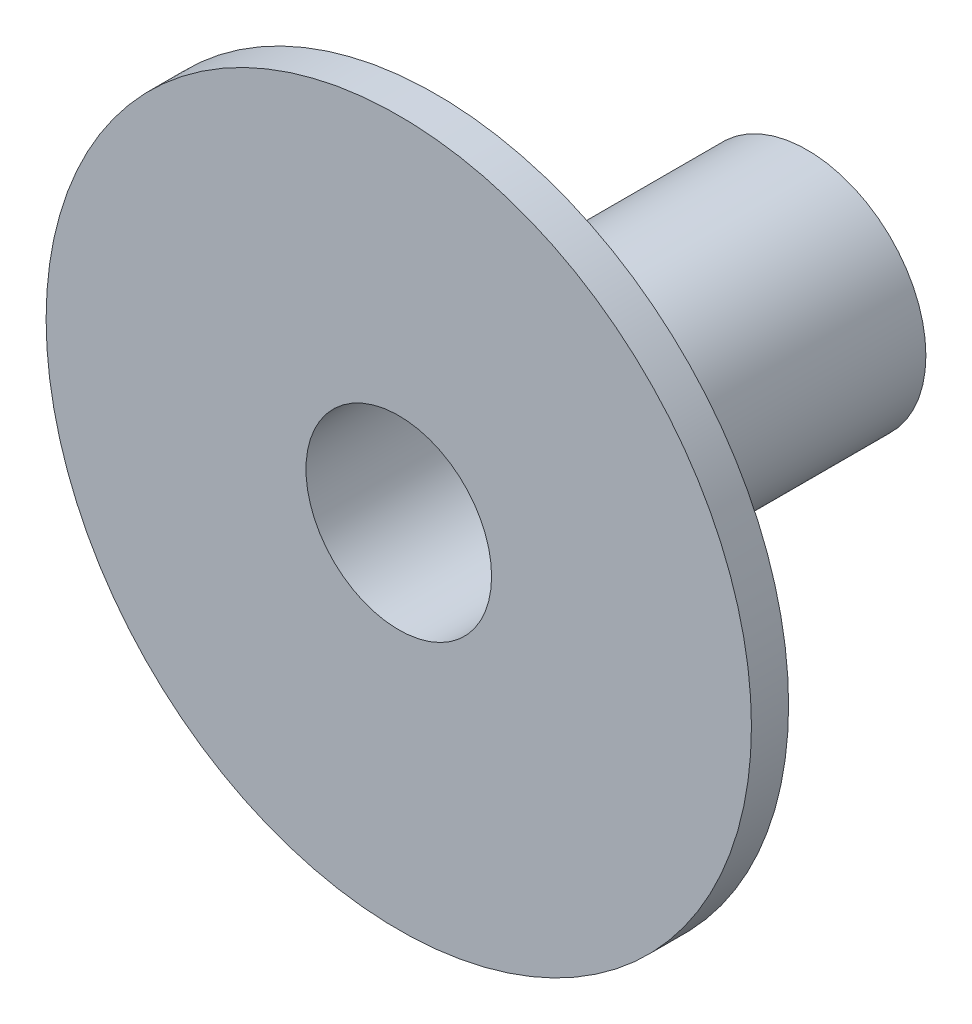
SolidWorks part; units mm, degrees
ref_plane "Front Plane" through (0, 0, 0) normal (0, 0, 1) x (1, 0, 0)
ref_plane "Top Plane" through (0, 0, 0) normal (0, 1, 0) x (1, 0, 0)
ref_plane "Right Plane" through (0, 0, 0) normal (1, 0, 0) x (0, 0, -1)
sketch "Sketch2" plane through (0, 0, 0) normal (1, 0, 0) x (0, 0, -1)
  line L0 (0, 0) -> (0, 9.4996)
  line L1 (0, 9.4996) -> (1.0008, 9.4996)
  line L2 (1.0008, 9.4996) -> (1.0008, 0)
  line L3 (0, 9.4996) -> (0, 2.4996)
  line L4 (1.0008, 0) -> (0, 0)
revolve "Revolve1" add sketch "Sketch2" angle 360 about L4 region at (0, 4.7498, -0.5004)
sketch "Sketch3" plane through (0, 0, 0) normal (0, 0, 1) x (1, 0, 0)
  circle A0 centre (0, 0) radius 2.5
extrude "Cut-Extrude1" cut sketch "Sketch3" against normal blind 2.54
sketch "Sketch4" plane through (0, 0, -1.0008) normal (0, 0, -1) x (-1, 0, 0)
  circle A0 centre (0, 0) radius 2.5
  circle A1 centre (0, 0) radius 3.1979
extrude "Boss-Extrude1" add sketch "Sketch4" along normal blind 10
